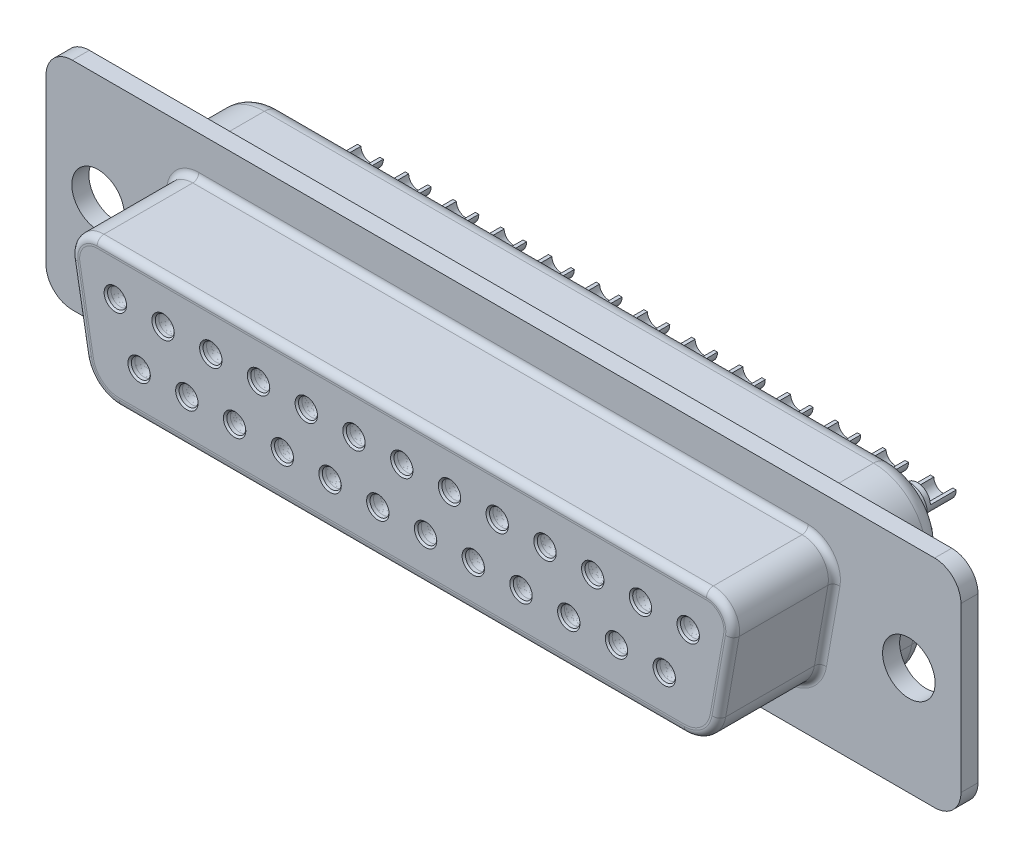
SolidWorks part; units mm, degrees
ref_plane "Front Plane" through (0, 0, 0) normal (0, 0, 1) x (1, 0, 0)
ref_plane "Top Plane" through (0, 0, 0) normal (0, 1, 0) x (1, 0, 0)
ref_plane "Right Plane" through (0, 0, 0) normal (1, 0, 0) x (0, 0, -1)
ref_plane "Plane1" through (0, 0, 6.89) normal (0, 0, 1) x (1, 0, 0)
ref_plane "Plane2" through (0, 0, -3.81) normal (0, 0, 1) x (1, 0, 0)
ref_plane "Plane3" through (0, 0, -4.91) normal (0, 0, 1) x (1, 0, 0)
sketch "Sketch3" plane through (0, 0, 0) normal (0, 0, 1) x (1, 0, 0)
  line L8 (25.019, 6.2738) -> (-25.019, 6.2738)
  line L9 (-26.543, 4.7498) -> (-26.543, -4.7498)
  line L10 (-25.019, -6.2738) -> (25.019, -6.2738)
  line L11 (26.543, -4.7498) -> (26.543, 4.7498)
  circle A0 centre (-23.5204, 0) radius 1.524
  circle A1 centre (23.5204, 0) radius 1.524
  arc A8 (-25.019, 6.2738) -> (-26.543, 4.7498) centre (-25.019, 4.7498) ccw
  arc A9 (-26.543, -4.7498) -> (-25.019, -6.2738) centre (-25.019, -4.7498) ccw
  arc A10 (25.019, -6.2738) -> (26.543, -4.7498) centre (25.019, -4.7498) ccw
  arc A11 (26.543, 4.7498) -> (25.019, 6.2738) centre (25.019, 4.7498) ccw
extrude "Flange" add sketch "Sketch3" along normal blind 0.99
sketch "Sketch5" plane through (0, 0, 6.89) normal (0, 0, 1) x (1, 0, 0)
  line L4 (17.6762, 3.9497) -> (-17.6762, 3.9497)
  line L5 (-19.177, 2.1611) -> (-18.3956, -2.2706)
  line L6 (-16.3945, -3.9497) -> (16.3945, -3.9497)
  line L7 (18.3956, -2.2706) -> (19.177, 2.1611)
  arc A5 (-17.6762, 3.9497) -> (-19.2002, 2.4257) centre (-17.6762, 2.4257) ccw
  arc A6 (-19.2002, 2.4257) -> (-19.177, 2.1611) centre (-17.6762, 2.4257) ccw
  arc A7 (-18.3956, -2.2706) -> (-16.3945, -3.9497) centre (-16.3945, -1.9177) ccw
  arc A8 (16.3945, -3.9497) -> (18.3956, -2.2706) centre (16.3945, -1.9177) ccw
  arc A9 (19.177, 2.1611) -> (17.6762, 3.9497) centre (17.6762, 2.4257) ccw
extrude "Front Steel Housing" add sketch "Sketch5" against normal blind 5.9
fillet "Fillet1" radius 0.4 8 edges at (18.8436, 3.4053, 6.89) (18.7863, -0.0547, 6.89) (17.7006, -3.4743, 6.89) (0, -3.9497, 6.89) (-17.7006, -3.4743, 6.89) (-18.7863, -0.0547, 6.89) (-18.8436, 3.4053, 6.89) (0, 3.9497, 6.89)
fillet "Fillet2" radius 0.35 8 edges at (18.8436, 3.4053, 0.99) (18.7863, -0.0547, 0.99) (17.7006, -3.4743, 0.99) (0, -3.9497, 0.99) (-17.7006, -3.4743, 0.99) (-18.7863, -0.0547, 0.99) (-18.8436, 3.4053, 0.99) (0, 3.9497, 0.99)
sketch "Sketch7" plane through (0, 0, -3.81) normal (0, 0, 1) x (1, 0, 0)
  line L1 (17.6762, 5.4737) -> (-17.6762, 5.4737)
  line L3 (19.8964, -2.5352) -> (20.6778, 1.8964)
  line L5 (-16.3945, -5.4737) -> (16.3945, -5.4737)
  line L7 (-20.6778, 1.8964) -> (-19.8964, -2.5352)
  arc A1 (20.7242, 2.4257) -> (17.6762, 5.4737) centre (17.6762, 2.4257) ccw
  arc A3 (20.6778, 1.8964) -> (20.7242, 2.4257) centre (17.6762, 2.4257) ccw
  arc A5 (16.3945, -5.4737) -> (19.8964, -2.5352) centre (16.3945, -1.9177) ccw
  arc A7 (-19.8964, -2.5352) -> (-16.3945, -5.4737) centre (-16.3945, -1.9177) ccw
  arc A9 (-20.7242, 2.4257) -> (-20.6778, 1.8964) centre (-17.6762, 2.4257) ccw
  arc A11 (-17.6762, 5.4737) -> (-20.7242, 2.4257) centre (-17.6762, 2.4257) ccw
extrude "Rear Steel Housing" add sketch "Sketch7" along normal blind 3.81
sketch "Sketch6" plane through (0, 0, 6.89) normal (0, 0, 1) x (1, 0, 0)
  line L4 (17.6762, 3.4417) -> (-17.6762, 3.4417)
  line L5 (-18.6767, 2.2493) -> (-17.8953, -2.1823)
  line L6 (-16.3945, -3.4417) -> (16.3945, -3.4417)
  line L7 (17.8953, -2.1823) -> (18.6767, 2.2493)
  arc A5 (-17.6762, 3.4417) -> (-18.6922, 2.4257) centre (-17.6762, 2.4257) ccw
  arc A6 (-18.6922, 2.4257) -> (-18.6767, 2.2493) centre (-17.6762, 2.4257) ccw
  arc A7 (-17.8953, -2.1823) -> (-16.3945, -3.4417) centre (-16.3945, -1.9177) ccw
  arc A8 (16.3945, -3.4417) -> (17.8953, -2.1823) centre (16.3945, -1.9177) ccw
  arc A9 (18.6767, 2.2493) -> (17.6762, 3.4417) centre (17.6762, 2.4257) ccw
extrude "Insert Cutout" cut sketch "Sketch6" against normal through all
sketch "Sketch8" plane through (0, 0, -3.81) normal (0, 0, 1) x (1, 0, 0)
  line L9 (17.6762, 3.4417) -> (-17.6762, 3.4417)
  line L10 (-18.6767, 2.2493) -> (-17.8953, -2.1823)
  line L11 (-16.3945, -3.4417) -> (16.3945, -3.4417)
  line L12 (17.8953, -2.1823) -> (18.6767, 2.2493)
  arc A10 (-17.6762, 3.4417) -> (-18.6922, 2.4257) centre (-17.6762, 2.4257) ccw
  arc A11 (-18.6922, 2.4257) -> (-18.6767, 2.2493) centre (-17.6762, 2.4257) ccw
  arc A12 (-17.8953, -2.1823) -> (-16.3945, -3.4417) centre (-16.3945, -1.9177) ccw
  arc A13 (16.3945, -3.4417) -> (17.8953, -2.1823) centre (16.3945, -1.9177) ccw
  arc A14 (18.6767, 2.2493) -> (17.6762, 3.4417) centre (17.6762, 2.4257) ccw
extrude "Plastic Insert" add sketch "Sketch8" along normal up to vertex (10.7 mm away) and the other way blind 1.1 separate body up to point (-17.6761, 3.4417, 6.89)
fillet "Fillet3" radius 1 8 edges at (20.0111, 4.3849, -3.81) (20.2871, -0.3194, -3.81) (18.6802, -4.6418, -3.81) (0, -5.4737, -3.81) (-18.6802, -4.6418, -3.81) (-20.2871, -0.3194, -3.81) (-20.0111, 4.3849, -3.81) (0, 5.4737, -3.81)
fillet "Fillet4" radius 0.4 8 edges at (20.0111, 4.3849, 0) (20.2871, -0.3194, 0) (18.6802, -4.6418, 0) (0, -5.4737, 0) (-18.6802, -4.6418, 0) (-20.2871, -0.3194, 0) (-20.0111, 4.3849, 0) (0, 5.4737, 0)
sketch "Sketch9" plane through (0, 0, 6.89) normal (0, 0, 1) x (1, 0, 0)
  line L0 (0, 3.5497) -> (0, -3.4417) construction
  line L1 (0, 0) -> (20.3222, 0) construction
  circle A0 centre (0, 1.42) radius 0.55
  circle A1 centre (2.77, 1.42) radius 0.55
  circle A2 centre (5.54, 1.42) radius 0.55
  circle A3 centre (8.31, 1.42) radius 0.55
  circle A4 centre (11.08, 1.42) radius 0.55
  circle A5 centre (13.85, 1.42) radius 0.55
  circle A6 centre (16.62, 1.42) radius 0.55
  circle A7 centre (-2.77, 1.42) radius 0.55
  circle A8 centre (-5.54, 1.42) radius 0.55
  circle A9 centre (-8.31, 1.42) radius 0.55
  circle A10 centre (-11.08, 1.42) radius 0.55
  circle A11 centre (-13.85, 1.42) radius 0.55
  circle A12 centre (-16.62, 1.42) radius 0.55
  circle A13 centre (1.38, -1.42) radius 0.55
  circle A14 centre (4.15, -1.42) radius 0.55
  circle A15 centre (6.92, -1.42) radius 0.55
  circle A16 centre (9.69, -1.42) radius 0.55
  circle A17 centre (12.46, -1.42) radius 0.55
  circle A18 centre (15.23, -1.42) radius 0.55
  circle A19 centre (-1.39, -1.42) radius 0.55
  circle A20 centre (-4.16, -1.42) radius 0.55
  circle A21 centre (-6.93, -1.42) radius 0.55
  circle A22 centre (-9.7, -1.42) radius 0.55
  circle A23 centre (-12.47, -1.42) radius 0.55
  circle A24 centre (-15.24, -1.42) radius 0.55
  dimension "D1" = 7
  dimension "D3" = 6
  dimension "D2" = 7
  dimension "D4" = 7
extrude "Cut-Extrude2" cut sketch "Sketch9" against normal through all
sketch "Sketch10" plane through (0, 0, -4.91) normal (0, 0, 1) x (1, 0, 0)
  circle A0 centre (16.62, 1.42) radius 0.75
  circle A22 centre (16.62, 1.42) radius 0.55
extrude "13 Solder Pins" add sketch "Sketch10" against normal blind 3
sketch "Sketch12" plane through (0, 0, -7.91) normal (0, 0, -1) x (-1, 0, 0)
  line L0 (-17.37, 1.42) -> (-15.87, 1.42)
  circle A0 centre (-16.62, 1.42) radius 0.75 construction
  arc A1 (-15.87, 1.42) -> (-17.37, 1.42) centre (-16.62, 1.42) ccw
extrude "Solder Pin Shape" cut sketch "Sketch12" against normal blind 1.5
pattern_linear "LPattern1" count 13 spacing 2.77 along (-1, 0, 0) of "13 Solder Pins", "Solder Pin Shape"
sketch "Sketch13" plane through (0, 0, -4.91) normal (0, 0, 1) x (1, 0, 0)
  circle A0 centre (15.23, -1.42) radius 0.55
  circle A1 centre (15.23, -1.42) radius 0.75
extrude "12 Solder Pins" add sketch "Sketch13" against normal blind 3
sketch "Sketch14" plane through (0, 0, -7.91) normal (0, 0, -1) x (-1, 0, 0)
  line L0 (-15.98, -1.42) -> (-14.48, -1.42)
  arc A0 (-15.98, -1.42) -> (-14.48, -1.42) centre (-15.23, -1.42) ccw
extrude "12 Solder Pin Shape" cut sketch "Sketch14" against normal blind 1.5
pattern_linear "LPattern2" count 12 spacing 2.77 along (-1, 0, 0) of "12 Solder Pin Shape", "12 Solder Pins"
sketch "Sketch15" plane through (0, 0, -4.91) normal (0, 0, 1) x (1, 0, 0)
  circle A0 centre (16.62, 1.42) radius 0.75
  circle A1 centre (16.62, 1.42) radius 0.55
  circle A2 centre (13.85, 1.42) radius 0.75
  circle A3 centre (13.85, 1.42) radius 0.55
  circle A4 centre (11.08, 1.42) radius 0.75
  circle A5 centre (11.08, 1.42) radius 0.55
  circle A6 centre (8.31, 1.42) radius 0.75
  circle A7 centre (8.31, 1.42) radius 0.55
  circle A8 centre (5.54, 1.42) radius 0.75
  circle A9 centre (5.54, 1.42) radius 0.55
  circle A10 centre (2.77, 1.42) radius 0.75
  circle A11 centre (2.77, 1.42) radius 0.55
  circle A12 centre (0, 1.42) radius 0.75
  circle A13 centre (0, 1.42) radius 0.55
  circle A14 centre (-2.77, 1.42) radius 0.75
  circle A15 centre (-2.77, 1.42) radius 0.55
  circle A16 centre (-5.54, 1.42) radius 0.75
  circle A17 centre (-5.54, 1.42) radius 0.55
  circle A18 centre (-8.31, 1.42) radius 0.75
  circle A19 centre (-8.31, 1.42) radius 0.55
  circle A20 centre (-11.08, 1.42) radius 0.75
  circle A21 centre (-11.08, 1.42) radius 0.55
  circle A22 centre (-13.85, 1.42) radius 0.75
  circle A23 centre (-13.85, 1.42) radius 0.55
  circle A24 centre (-16.62, 1.42) radius 0.75
  circle A25 centre (-16.62, 1.42) radius 0.55
  circle A26 centre (15.23, -1.42) radius 0.55
  circle A27 centre (15.23, -1.42) radius 0.75
  circle A28 centre (12.46, -1.42) radius 0.55
  circle A29 centre (12.46, -1.42) radius 0.75
  circle A30 centre (9.69, -1.42) radius 0.55
  circle A31 centre (9.69, -1.42) radius 0.75
  circle A32 centre (6.92, -1.42) radius 0.55
  circle A33 centre (6.92, -1.42) radius 0.75
  circle A34 centre (4.15, -1.42) radius 0.55
  circle A35 centre (4.15, -1.42) radius 0.75
  circle A36 centre (1.38, -1.42) radius 0.55
  circle A37 centre (1.38, -1.42) radius 0.75
  circle A38 centre (-1.39, -1.42) radius 0.55
  circle A39 centre (-1.39, -1.42) radius 0.75
  circle A40 centre (-4.16, -1.42) radius 0.55
  circle A41 centre (-4.16, -1.42) radius 0.75
  circle A42 centre (-6.93, -1.42) radius 0.55
  circle A43 centre (-6.93, -1.42) radius 0.75
  circle A44 centre (-9.7, -1.42) radius 0.55
  circle A45 centre (-9.7, -1.42) radius 0.75
  circle A46 centre (-12.47, -1.42) radius 0.55
  circle A47 centre (-12.47, -1.42) radius 0.75
  circle A48 centre (-15.24, -1.42) radius 0.55
  circle A49 centre (-15.24, -1.42) radius 0.75
  dimension "D1" = 13
  dimension "D2" = 12
extrude "Boss-Extrude7" add sketch "Sketch15" along normal blind 11.5 separate body
chamfer "Chamfer1" distance 0.1 angle 45 25 edges at (-16.07, 1.42, 6.89) (-14.69, -1.42, 6.89) (-11.92, -1.42, 6.89) (-9.15, -1.42, 6.89) (-6.38, -1.42, 6.89) (-3.61, -1.42, 6.89) (-0.84, -1.42, 6.89) (1.93, -1.42, 6.89) (4.7, -1.42, 6.89) (7.47, -1.42, 6.89) (10.24, -1.42, 6.89) (13.01, -1.42, 6.89) (15.78, -1.42, 6.89) (17.17, 1.42, 6.89) (14.4, 1.42, 6.89) (11.63, 1.42, 6.89) (8.86, 1.42, 6.89) (6.09, 1.42, 6.89) (3.32, 1.42, 6.89) (0.55, 1.42, 6.89) (-2.22, 1.42, 6.89) (-4.99, 1.42, 6.89) (-7.76, 1.42, 6.89) (-10.53, 1.42, 6.89) (-13.3, 1.42, 6.89)
ref_plane "Płaszczyzna1" through (0, 0, 0) normal (0, -1, 0) x (-1, 0, 0)
ref_plane "Płaszczyzna2" through (0, 0, 0) normal (1, 0, 0) x (0, 0, -1)
